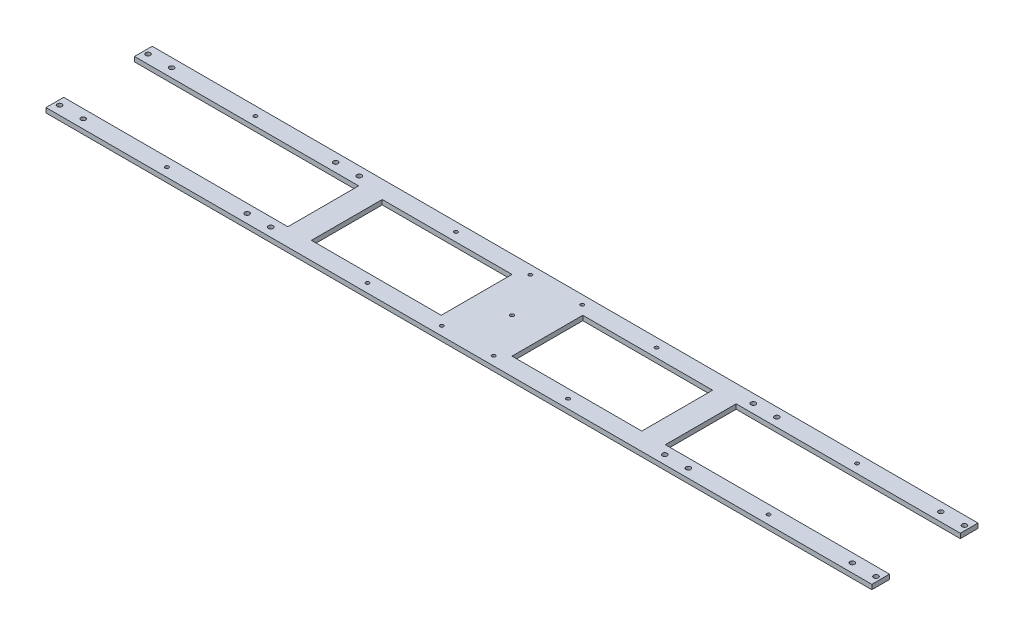
SolidWorks part; units mm, degrees
ref_plane "前视基准面" through (0, 0, 0) normal (0, 0, 1) x (1, 0, 0)
ref_plane "上视基准面" through (0, 0, 0) normal (0, 1, 0) x (1, 0, 0)
ref_plane "右视基准面" through (0, 0, 0) normal (1, 0, 0) x (0, 0, -1)
other "Configuration Table"
sketch "草图1" plane through (0, 0, 0) normal (0, 1, 0) x (1, 0, 0)
  line L1 (-350, -45) -> (350, -45)
  line L2 (-350, -45) -> (-350, 45)
  line L3 (-350, 45) -> (350, 45)
  line L4 (350, -45) -> (350, 45)
  line L5 (-350, -45) -> (350, 45) construction
  line L6 (-350, 45) -> (350, -45) construction
  line L7 (-140, -30) -> (140, -30)
  line L8 (-140, -30) -> (-140, 30)
  line L9 (-140, 30) -> (140, 30)
  line L10 (140, -30) -> (140, 30)
  line L11 (-140, -30) -> (140, 30) construction
  line L12 (-140, 30) -> (140, -30) construction
  point P0 (0, 0)
  point P6 (0, 0)
  dimension "D1" = 700
  dimension "D2" = 90
  dimension "D3" = 60
  dimension "D4" = 280
extrude "凸台-拉伸1" add sketch "草图1" along normal blind 4
sketch "草图2" plane through (0, 4, 0) normal (0, 1, 0) x (1, 0, 0)
  line L0 (-350, 45) -> (-350, -45) construction
  line L1 (-350, -30) -> (-160, -30)
  line L2 (-350, -30) -> (-350, 30)
  line L3 (-350, 30) -> (-160, 30)
  line L4 (-160, -30) -> (-160, 30)
  line L5 (140, 30) -> (-140, 30) construction
  line L6 (-140, -30) -> (140, -30) construction
  line L7 (-140, 30) -> (-140, -30) construction
  dimension "D1" = 20
extrude "切除-拉伸1" cut sketch "草图2" against normal blind 4
mirror "镜向1" about plane through (0, 0, 0) normal (1, 0, 0) of "切除-拉伸1"
sketch "草图4" plane through (0, 4, 0) normal (0, 1, 0) x (1, 0, 0)
  line L0 (350, 45) -> (-350, 45) construction
  line L2 (-350, 45) -> (-350, 30) construction
  circle A0 centre (-187, 37.5) radius 2
  circle A1 centre (-167, 37.5) radius 2
  circle A2 centre (-346, 37.5) radius 2
  circle A3 centre (-326, 37.5) radius 2
  point P8 (0, 0)
  point P9 (-214.6775, 40.4674)
  dimension "D1" = 4
  dimension "D3" = 4
  dimension "D2" = 20
  dimension "D4" = 20
  dimension "D5" = 7.5
  dimension "D6" = 167
  dimension "D7" = 4
extrude "切除-拉伸2" cut sketch "草图4" against normal blind 15
mirror "镜向2" about plane through (0, 0, 0) normal (1, 0, 0) of "切除-拉伸2" second plane through (0, 0, 0) second plane normal (0, 0, 1)
sketch "草图5" plane through (0, 4, 0) normal (0, 1, 0) x (1, 0, 0)
  line L0 (140, 30) -> (-140, 30) construction
  line L1 (-30, -30) -> (30, -30)
  line L2 (-30, -30) -> (-30, 30)
  line L3 (-30, 30) -> (30, 30)
  line L4 (30, -30) -> (30, 30)
  line L5 (-30, -30) -> (30, 30) construction
  line L6 (-30, 30) -> (30, -30) construction
  point P0 (0, 0)
  dimension "D1" = 60
extrude "凸台-拉伸2" add sketch "草图5" against normal blind 4
sketch "草图6" plane through (0, 4, 0) normal (0, 1, 0) x (1, 0, 0)
  line L0 (350, 45) -> (-350, 45) construction
  line L1 (-85, 37.5) -> (-85, 30) construction
  line L2 (-30, 30) -> (-140, 30) construction
  line L3 (-255, 37.5) -> (-255, 30) construction
  line L4 (-160, 30) -> (-350, 30) construction
  line L5 (-30, 30) -> (-30, -30) construction
  circle A0 centre (-255, 37.5) radius 1.5
  circle A1 centre (-85, 37.5) radius 1.5
  circle A2 centre (0, 0) radius 1.5
  circle A3 centre (-22, 37.5) radius 1.5
  point P14 (0, 0)
  dimension "D1" = 3
  dimension "D3" = 8
  dimension "D2" = 7.5
extrude "切除-拉伸3" cut sketch "草图6" against normal blind 4
mirror "镜向3" about plane through (0, 0, 0) normal (0, 0, 1) of "切除-拉伸3" second plane through (0, 0, 0) second plane normal (1, 0, 0)
